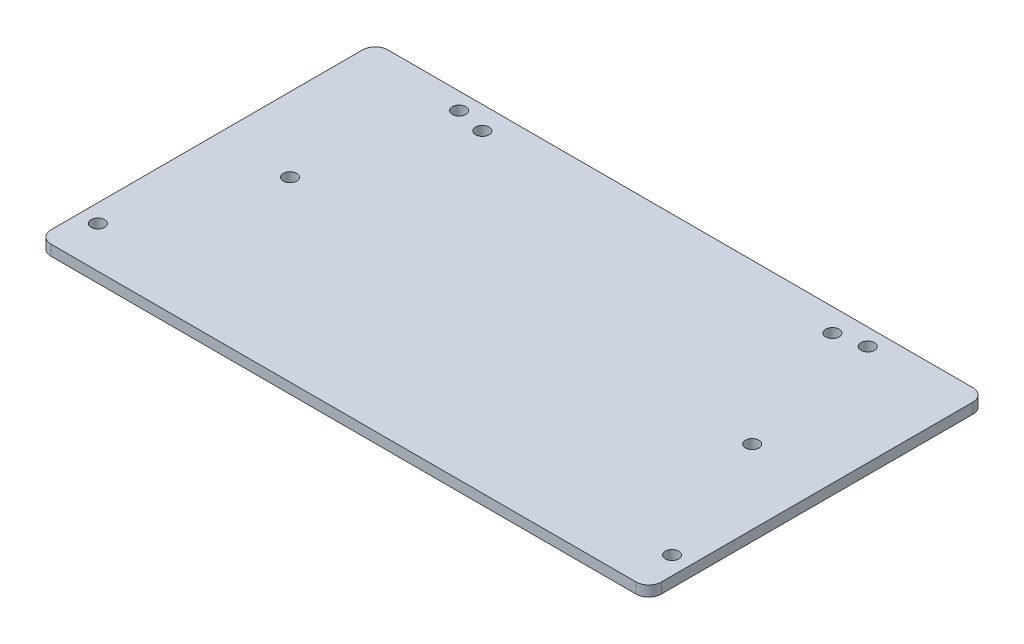
SolidWorks part; units mm, degrees
ref_plane "Front Plane" through (0, 0, 0) normal (0, 0, 1) x (1, 0, 0)
ref_plane "Top Plane" through (0, 0, 0) normal (0, 1, 0) x (1, 0, 0)
ref_plane "Right Plane" through (0, 0, 0) normal (1, 0, 0) x (0, 0, -1)
sketch "Sketch1" plane through (0, 0, 0) normal (0, 1, 0) x (1, 0, 0)
  line L0 (0, 0) -> (0, -101.6)
  line L1 (0, -101.6) -> (184.15, -101.6)
  line L2 (184.15, -101.6) -> (184.15, 0)
  line L3 (184.15, 0) -> (0, 0)
  dimension "D1" = 184.15
  dimension "D3" = 101.6
extrude "Boss-Extrude1" add sketch "Sketch1" along normal blind 3.175 contours L2 L3 L0 L1 region at (92.075, 0, 50.8)
fillet "Fillet1" radius 3.81 4 edges at (184.15, 1.5875, 0) (184.15, 1.5875, 101.6) (0, 1.5875, 0) (0, 1.5875, 101.6)
sketch "Sketch2" plane through (0, 3.175, 0) normal (0, 1, 0) x (1, 0, 0)
  line L0 (92.075, 0) -> (92.075, -101.6) construction
  line L1 (180.34, 0) -> (3.81, 0) construction
  line L2 (3.81, -101.6) -> (180.34, -101.6) construction
  circle A4 centre (5.4374, -89.1463) radius 2.032 construction
  circle A5 centre (5.4374, -89.1463) radius 2.032
  circle A6 centre (22.3389, -48.035) radius 2.032 construction
  circle A7 centre (39.2404, -6.9237) radius 2.032 construction
  circle A8 centre (30.4063, -5.1114) radius 2.032 construction
  circle A9 centre (22.3389, -48.035) radius 2.032
  circle A10 centre (39.2404, -6.9237) radius 2.032
  circle A11 centre (30.4063, -5.1114) radius 2.032
  circle A12 centre (178.7126, -89.1463) radius 2.032
  circle A13 centre (161.8111, -48.035) radius 2.032
  circle A14 centre (153.7437, -5.1114) radius 2.032
  circle A15 centre (144.9096, -6.9237) radius 2.032
extrude "Cut-Extrude1" cut sketch "Sketch2" against normal through all contours A11 | A9 | A5 | A12 | A13 | A15 | A14 | A10 region at (5.4374, 3.175, 89.1463) region at (22.3389, 3.175, 48.035) region at (30.4063, 3.175, 5.1114) region at (178.7126, 3.175, 89.1463) region at (161.8111, 3.175, 48.035) region at (153.7437, 3.175, 5.1114) region at (144.9096, 3.175, 6.9237)
